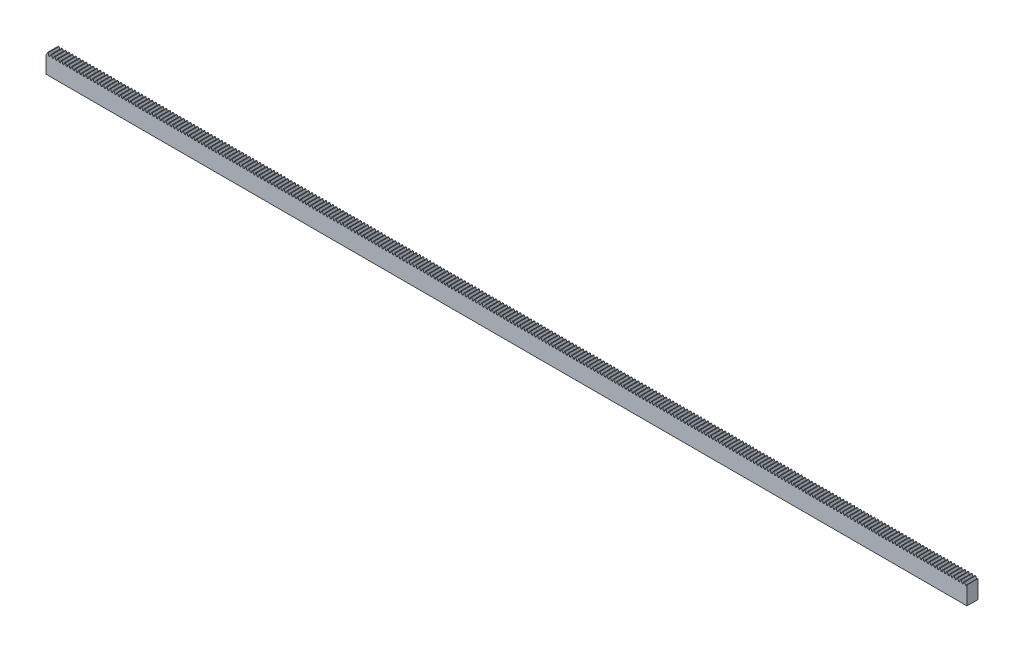
SolidWorks part; units mm, degrees
extrude "Blank" add sketch "BlankSke" against normal blind 6
sketch "BlankSke" plane through (0, 0, 0) normal (0, 0, 1) x (1, 0, 0)
  line L1 (0, 0) -> (500, 0)
  line L2 (0, 0) -> (0, 10.6)
  line L3 (0, 10.6) -> (500, 10.6)
  line L4 (500, 0) -> (500, 10.6)
  dimension "Length" = 500
material "ABS PC"
ref_plane "Plane1" through (0, 0, 0) normal (0, 0, 1) x (1, 0, 0)
ref_plane "Plane2" through (0, 0, 0) normal (0, 1, 0) x (1, 0, 0)
ref_plane "Plane3" through (0, 0, 0) normal (1, 0, 0) x (0, 0, -1)
sketch "HoldingSke" plane through (0, 0, 0) normal (0, 1, 0) x (1, 0, 0)
  line L0 (0, 0) -> (0.232, 1.6504)
  line L1 (-15, 0) -> (100, 0) construction
  line L2 (0, 0) -> (-2.1039, 2.3779)
  line L3 (0, 0) -> (-11.863, 4.5341)
  line L4 (0, 0) -> (-0.452, -8.6242)
  line L5 (0, 0) -> (-23.7986, -8.8762)
  line L6 (0, 0) -> (-10.5278, -7.1032)
  line L9 (-71.009, 38.7566) -> (398.8373, 209.7667)
  line L10 (-76.2, 2.9779) -> (-66.2, 2.9779)
  line L11 (0, 0) -> (-6, 0)
  line L12 (-76.2, 101.6) -> (-76.177, 101.6)
  line L13 (24.9733, 27.94) -> (52.9518, 28.4284)
  line L14 (24.9733, 27.94) -> (24.9743, 27.94)
  line L15 (24.9733, 27.94) -> (100.4006, 29.5858)
  circle A0 centre (0, 0) radius 19.05
  circle A1 centre (0, 0) radius 5
  circle A2 centre (0, 0) radius 12.7
  dimension "Num_teeth" = 267
  dimension "Width" = 6
  dimension "Length" = 500
  dimension "Pitch_height" = 10
sketch "TooCutSkeIll" plane through (0, 0, 0) normal (0, 0, 1) x (1, 0, 0)
  line L0 (-0.7529, 10.5842) -> (-0.3034, 9.3494)
  line L1 (-0.1615, 9.25) -> (0.1615, 9.25)
  line L2 (0.3034, 9.3494) -> (0.7529, 10.5842)
  line L3 (500, 10.6) -> (0, 10.6) construction
  line L4 (0, 0) -> (0, 64.897) construction
  line L5 (-13.208, 10) -> (12.954, 10) construction
  line L6 (0, 0) -> (500, 0) construction
  line L7 (0.5402, 10) -> (0.5402, 48.7463) construction
  line L8 (-0.5402, 10) -> (-0.5402, 48.7463) construction
  line L9 (0.7754, 10.6) -> (0.7754, 10.6254)
  line L10 (-0.7754, 10.6) -> (-0.7754, 10.6254)
  line L11 (-0.7754, 10.6254) -> (0.7754, 10.6254)
  arc A0 (0.1615, 9.25) -> (0.3034, 9.3494) centre (0.1615, 9.401) ccw
  arc A1 (-0.3034, 9.3494) -> (-0.1615, 9.25) centre (-0.1615, 9.401) ccw
  arc A2 (0.7754, 10.6) -> (0.7529, 10.5842) centre (0.7754, 10.576) ccw
  arc A3 (-0.7529, 10.5842) -> (-0.7754, 10.6) centre (-0.7754, 10.576) ccw
  dimension "Addendum_plus" = 0.6254
  dimension "Pitch_height" = 10
  dimension "Pressure_angle" = 20
  dimension "Gap_width" = 1.0805
  dimension "Dedendum" = 0.75
extrude "ToothCutIll" [suppressed] cut sketch "TooCutSkeIll" against normal through all
sketch "TooCutSkeSim" plane through (0, 0, 0) normal (0, 0, 1) x (1, 0, 0)
  line L0 (0.2673, 9.25) -> (-0.2673, 9.25)
  line L1 (0.7679, 10.6254) -> (0.2673, 9.25)
  line L2 (0, 17.4625) -> (0, 53.467) construction
  line L3 (0.7679, 10.6254) -> (-0.7679, 10.6254)
  line L6 (-0.7679, 10.6254) -> (-0.2673, 9.25)
  line L9 (-0.5402, 10) -> (0.5402, 10) construction
  line L10 (0, 0) -> (500, 0) construction
  line L11 (0.5402, 10) -> (0.5402, 53.467) construction
  line L12 (-0.5402, 10) -> (-0.5402, 53.467) construction
  dimension "Addendum_plus" = 0.6254
  dimension "Pitch_height" = 10
  dimension "Pressure_angle" = 20
  dimension "Gap_width" = 1.0805
  dimension "Dedendum" = 0.75
extrude "ToothCutSim" cut sketch "TooCutSkeSim" against normal through all
pattern_linear "TeethCuts" count 266 spacing 1.885 along (1, 0, 0) of "ToothCutIll", "ToothCutSim"
equation "' \"Module@HoldingSke\" = 6.35"
equation "' \"Num_teeth@HoldingSke\" = 12"
equation "' \"Ap@HoldingSke\" =  20"
equation "' \"Ap@HoldingSke\" = 20"
equation "' \"Width@HoldingSke\" = 0.25 * 25.4"
equation "' \"Show_teeth@HoldingSke\" = 500"
equation "' \"Backlash@HoldingSke\" = 0.009 * 25.4"
equation "' \"Addendum_fac@HoldingSke\" = 1.0"
equation "' \"Dedendum_fac@HoldingSke\" = 1.25"
equation "' \"Dedendum_add@HoldingSke\" = 0.00005 * 25.4"
equation "' \"Clearance_fac@HoldingSke\" = 0.25"
equation "' \"Pitch_height@HoldingSke\" = 1 * 25.4"
equation "' \"Length@HoldingSke\" = 4.71 * 25.4"
equation "\"Pitch@HoldingSke\" = 1 / \"Module@HoldingSke\""
equation "\"MPH@HoldingSke\" = \"Dedendum_fac@HoldingSke\" / \"Pitch@HoldingSke\" + 2 * \"Dedendum_add@HoldingSke\" + 0.002 * 25.4"
equation "\"MPH@HoldingSke\" = ((sgn( \"MPH@HoldingSke\" - \"Pitch_height@HoldingSke\")+1)*( \"MPH@HoldingSke\" - \"Pitch_height@HoldingSke\"))/2 + \"Pitch_height@HoldingSke\""
equation "\"Blank_height@BlankSke\" = \"Pitch_height@HoldingSke\" + \"Addendum_fac@HoldingSke\"  / \"Pitch@HoldingSke\" "
equation "\"Length@BlankSke\" =  \"Length@HoldingSke\""
equation "\"Face_width@Blank\" = \"Width@HoldingSke\""
equation "\"Pressure_angle@TooCutSkeIll\" = \"Ap@HoldingSke\""
equation "\"Addendum_plus@TooCutSkeIll\" =  \"Addendum_fac@HoldingSke\"  / \"Pitch@HoldingSke\" + 0.001 *25.4"
equation "\"Dedendum@TooCutSkeIll\" = \"Dedendum_fac@HoldingSke\"  / \"Pitch@HoldingSke\""
equation "\"Pitch_height@TooCutSkeIll\" =  \"MPH@HoldingSke\""
equation "\"Gap_width@TooCutSkeIll\" = 3.14159265 / 2 / \"Pitch@HoldingSke\" + 6 * \"Backlash@HoldingSke\""
equation "\"Pressure_angle@TooCutSkeSim\" = \"Ap@HoldingSke\""
equation "\"Addendum_plus@TooCutSkeSim\" =  \"Addendum_fac@HoldingSke\"  / \"Pitch@HoldingSke\" + 0.001 * 25.4"
equation "\"Dedendum@TooCutSkeSim\" = \"Dedendum_fac@HoldingSke\"  / \"Pitch@HoldingSke\""
equation "\"Pitch_height@TooCutSkeSim\" =  \"MPH@HoldingSke\""
equation "\"Gap_width@TooCutSkeSim\" = 3.14159265 / 2 / \"Pitch@HoldingSke\" + 6 * \"Backlash@HoldingSke\""
equation "\"Root_fillet@TooCutSkeIll\" = \"Clearance_fac@HoldingSke\" / \"Pitch@HoldingSke\" + \"Dedendum_add@HoldingSke\""
equation "\"Break_rad@TooCutSkeIll\" = 0.02 / \"Pitch@HoldingSke\" * 2"
equation "\"Linear_pitch@TeethCuts\" = 3.14159265 / \"Pitch@HoldingSke\""
equation "\"Num_teeth@HoldingSke\" = int( ( \"Length@HoldingSke\" + 0 ) / (3.14159265 / \"Pitch@HoldingSke\")) + 0.9999  + 1"
equation " \"Num_teeth@TeethCuts\" = int( \"Show_teeth@HoldingSke\" ) + 1"
equation " \"Num_teeth@TeethCuts\" = ((sgn( \"Num_teeth@TeethCuts\" - \"Num_teeth@HoldingSke\" )-1)*( \"Num_teeth@TeethCuts\" - \"Num_teeth@HoldingSke\" ))/-2+ \"Num_teeth@HoldingSke\""
equation " \"Num_teeth@TeethCuts\" = ((sgn( \"Num_teeth@TeethCuts\" - 2.0)+1)*( \"Num_teeth@TeethCuts\" - 2.0))/2 +2.0"
